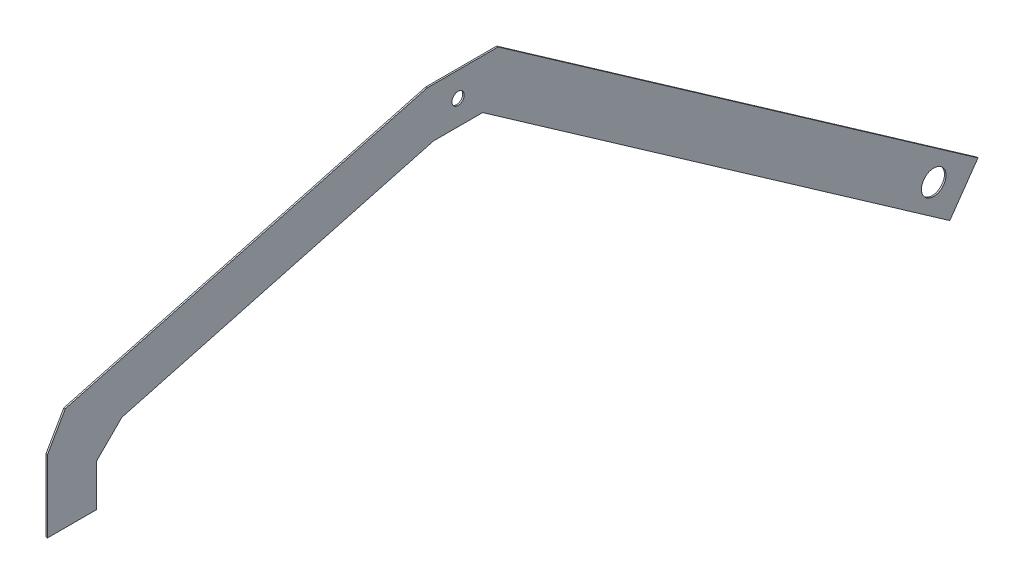
SolidWorks part; units mm, degrees
material "6061 Alloy"
ref_plane "Front Plane" through (0, 0, 0) normal (0, 0, 1) x (1, 0, 0)
ref_plane "Top Plane" through (0, 0, 0) normal (0, 1, 0) x (1, 0, 0)
ref_plane "Right Plane" through (0, 0, 0) normal (1, 0, 0) x (0, 0, -1)
sketch "Sketch1" plane through (0, 0, 0) normal (1, 0, 0) x (0, 0, -1)
  line L11 (-32.0879, 25.4) -> (41.4172, 25.4)
  line L12 (-25.4, -25.4) -> (25.4, -25.4)
  line L13 (0, -25.4) -> (0, 0) construction
  line L14 (25.4, -25.4) -> (508.605, -363.7438)
  line L15 (508.605, -363.7438) -> (537.7427, -322.1309)
  line L16 (537.7427, -322.1309) -> (41.4172, 25.4)
  line L17 (-32.0879, 25.4) -> (-424.6402, -79.7841)
  line L18 (-25.4, -25.4) -> (-373.8402, -118.7643)
  line L19 (-424.6402, -79.7841) -> (-424.6402, -181.3841)
  line L20 (-424.6402, -181.3841) -> (-373.8402, -181.3841)
  line L21 (-373.8402, -181.3841) -> (-373.8402, -118.7643)
  line L22 (523.1738, -342.9373) -> (491.9641, -321.0841) construction
  circle A0 centre (0, 0) radius 6.35
  circle A1 centre (491.9641, -321.0841) radius 12.7
  point P9 (0, 0)
  dimension "D1" = 12.7
  dimension "D13" = 25.4
  dimension "D2" = 50.8
  dimension "D3" = 50.8
  dimension "D4" = 35
  dimension "D5" = 50.8
  dimension "D6" = 15
  dimension "D7" = 25.4
  dimension "D8" = 25.4
  dimension "D9" = 139.7
  dimension "D10" = 101.6
  dimension "D11" = 50.8
  dimension "D12" = 406.4
  dimension "D14" = 38.1
extrude "Boss-Extrude1" add sketch "Sketch1" along normal blind 1.5875
chamfer "Chamfer1" distance 19.05 angle 45 1 edges at (0.7937, -118.7643, 373.8402) first distance on face at (0.7937, -150.0742, 373.8402)
chamfer "Chamfer2" distance 19.05 angle 45 1 edges at (0.7937, -79.7841, 424.6402) first distance on face at (0.7937, -27.192, 228.3641)
